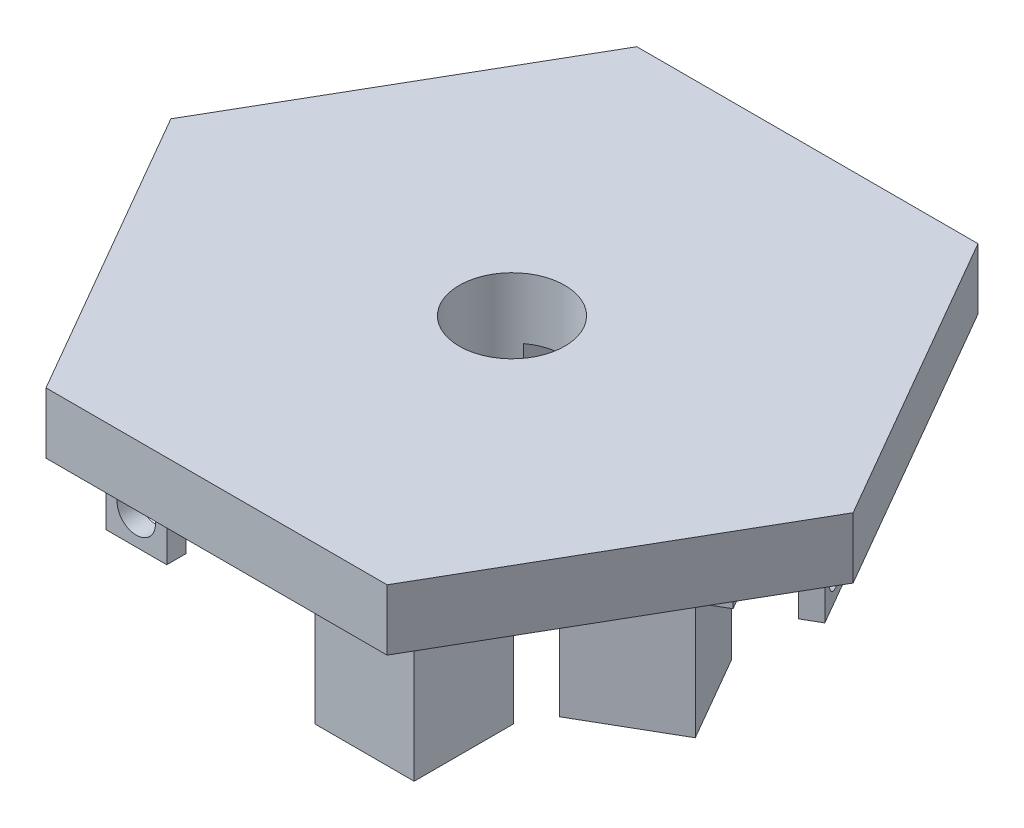
SolidWorks part; units mm, degrees
ref_plane "Front Plane" through (0, 0, 0) normal (0, 0, 1) x (1, 0, 0)
ref_plane "Top Plane" through (0, 0, 0) normal (0, 1, 0) x (1, 0, 0)
ref_plane "Right Plane" through (0, 0, 0) normal (1, 0, 0) x (0, 0, -1)
sketch "Sketch1" plane through (0, 0, 0) normal (0, 1, 0) x (1, 0, 0)
  line L1 (17.78, -30.7959) -> (35.56, 0)
  line L2 (35.56, 0) -> (17.78, 30.7959)
  line L3 (17.78, 30.7959) -> (-17.78, 30.7959)
  line L4 (-17.78, 30.7959) -> (-35.56, 0)
  line L5 (-35.56, 0) -> (-17.78, -30.7959)
  line L6 (-17.78, -30.7959) -> (17.78, -30.7959)
  circle A0 centre (0, 0) radius 30.7959 construction
  dimension "D1" = 35.56
extrude "Boss-Extrude1" add sketch "Sketch1" along normal blind 6.35 contours L4 L5 L6 L1 L2 L3
sketch "Sketch2" plane through (0, 0, 0) normal (0, -1, 0) x (1, 0, 0)
  line L0 (-5.175, 15.374) -> (-5.175, 5.024)
  line L5 (-3.175, 13.374) -> (3.175, 13.374)
  line L6 (-3.175, 13.374) -> (-3.175, 7.024)
  line L7 (-3.175, 7.024) -> (3.175, 7.024)
  line L8 (3.175, 13.374) -> (3.175, 7.024)
  line L9 (-3.175, 13.374) -> (3.175, 7.024) construction
  line L10 (-3.175, 7.024) -> (3.175, 13.374) construction
  line L11 (-5.175, 5.024) -> (-2.2382, 5.024)
  line L12 (5.175, 15.374) -> (5.175, 5.024)
  line L13 (-5.175, 15.374) -> (5.175, 15.374)
  line L14 (2.2382, 5.024) -> (5.175, 5.024)
  line L15 (-5.175, 5.024) -> (5.175, 5.024) construction
  line L16 (13.1697, -3.9374) -> (7.6705, -0.7624)
  line L17 (13.1697, -3.9374) -> (9.9947, -9.4366)
  line L18 (9.9947, -9.4366) -> (4.4955, -6.2616)
  line L19 (7.6705, -0.7624) -> (4.4955, -6.2616)
  line L20 (3.2318, -4.4503) -> (1.7634, -6.9937)
  line L21 (10.7268, -12.1687) -> (1.7634, -6.9937)
  line L22 (15.9018, -3.2053) -> (10.7268, -12.1687)
  line L23 (15.9018, -3.2053) -> (6.9384, 1.9697)
  line L24 (6.9384, 1.9697) -> (5.47, -0.5737)
  line L25 (-9.9947, -9.4366) -> (-4.4955, -6.2616)
  line L26 (-9.9947, -9.4366) -> (-13.1697, -3.9374)
  line L27 (-13.1697, -3.9374) -> (-7.6705, -0.7624)
  line L28 (-4.4955, -6.2616) -> (-7.6705, -0.7624)
  line L29 (-5.47, -0.5737) -> (-6.9384, 1.9697)
  line L30 (-15.9018, -3.2053) -> (-6.9384, 1.9697)
  line L31 (-10.7268, -12.1687) -> (-15.9018, -3.2053)
  line L32 (-10.7268, -12.1687) -> (-1.7634, -6.9937)
  line L33 (-1.7634, -6.9937) -> (-3.2318, -4.4503)
  circle A0 centre (0, 0) radius 5.5 construction
  arc A2 (-2.2382, 5.024) -> (2.2382, 5.024) centre (0, 0) cw
  arc A3 (5.47, -0.5737) -> (3.2318, -4.4503) centre (0, 0) cw
  arc A4 (-3.2318, -4.4503) -> (-5.47, -0.5737) centre (0, 0) cw
  point P3 (0, 10.199)
  point P37 (0, 0)
  dimension "D1" = 11
  dimension "D3" = 1.524
  dimension "D4" = 2
  dimension "D2" = 6.35
  dimension "D5" = 3
sketch "Sketch6" plane through (0, 6.35, 0) normal (0, 1, 0) x (1, 0, 0)
  circle A0 centre (0, 0) radius 5.5
  dimension "D1" = 11
extrude "Cut-Extrude1" cut sketch "Sketch6" against normal through all
extrude "Boss-Extrude2" add sketch "Sketch2" along normal blind 25.4
sketch "Sketch7" plane through (0, 0, 0) normal (0, -1, 0) x (1, 0, 0)
  line L0 (-14.5653, 20.7726) -> (-8.2153, 20.7726)
  line L1 (-8.2153, 20.7726) -> (-8.2153, 18.7726)
  line L2 (-8.2153, 18.7726) -> (-14.5653, 18.7726)
  line L3 (-14.5653, 18.7726) -> (-14.5653, 20.7726)
  line L5 (-17.78, 30.7959) -> (17.78, 30.7959) construction
  line L7 (-14.5653, 25.7726) -> (-14.5653, 27.7726)
  line L8 (-14.5653, 27.7726) -> (-8.2153, 27.7726)
  line L9 (-8.2153, 27.7726) -> (-8.2153, 25.7726)
  line L10 (-8.2153, 25.7726) -> (-14.5653, 25.7726)
  line L11 (-5.175, 15.374) -> (-5.175, 5.024) construction
  line L12 (25.2722, 2.2276) -> (22.0972, -3.2716)
  line L13 (22.0972, -3.2716) -> (20.3652, -2.2716)
  line L14 (20.3652, -2.2716) -> (23.5402, 3.2276)
  line L15 (23.5402, 3.2276) -> (25.2722, 2.2276)
  line L16 (29.6024, -0.2724) -> (31.3344, -1.2724)
  line L17 (31.3344, -1.2724) -> (28.1594, -6.7716)
  line L18 (28.1594, -6.7716) -> (26.4274, -5.7716)
  line L19 (26.4274, -5.7716) -> (29.6024, -0.2724)
  line L20 (-10.7069, -23.0002) -> (-13.8819, -17.501)
  line L21 (-13.8819, -17.501) -> (-12.1499, -16.501)
  line L22 (-12.1499, -16.501) -> (-8.9749, -22.0002)
  line L23 (-8.9749, -22.0002) -> (-10.7069, -23.0002)
  line L24 (-15.0371, -25.5002) -> (-16.7691, -26.5002)
  line L25 (-16.7691, -26.5002) -> (-19.9441, -21.001)
  line L26 (-19.9441, -21.001) -> (-18.2121, -20.001)
  line L27 (-18.2121, -20.001) -> (-15.0371, -25.5002)
  line L28 (-17.78, -30.7959) -> (-35.56, 0) construction
  line L29 (35.56, 0) -> (17.78, -30.7959) construction
  point P13 (-11.3903, 18.7726)
  dimension "D1" = 20.7726
  dimension "D2" = 2
  dimension "D4" = 5
  dimension "D5" = 6.2153
  dimension "D6" = 6.35
  dimension "D8" = 3.0233
  dimension "D9" = 3.0233
  dimension "D3" = 2
  dimension "D7" = 3
extrude "Boss-Extrude3" add sketch "Sketch7" along normal blind 6.35
sketch "Sketch9" plane through (0, 0, 27.7726) normal (0, 0, 1) x (1, 0, 0)
  line L0 (-8.2153, -6.35) -> (-14.5653, -6.35) construction
  line L1 (-17.78, 0) -> (17.78, 0) construction
  circle A0 centre (-11.3903, -3.2626) radius 2
  point P4 (-11.3903, -6.35)
  dimension "D1" = 4
  dimension "D2" = 3.2626
extrude "Cut-Extrude2" cut sketch "Sketch9" against normal blind 9.588
pattern_circular "CirPattern1" count 3 over 360 about axis through (0, 0, 0) along (0, 1, 0) of "Cut-Extrude2" reverse direction yes
